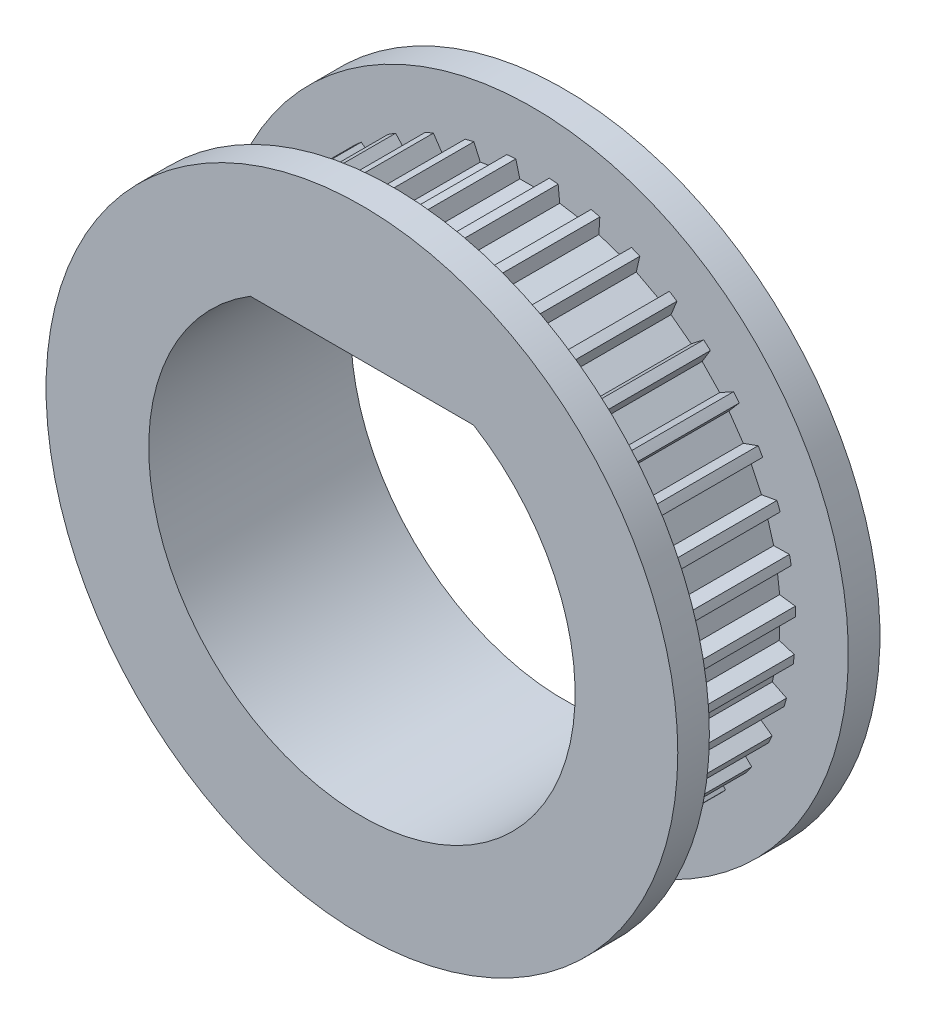
SolidWorks part; units mm, degrees
ref_plane "Front Plane" through (0, 0, 0) normal (0, 0, 1) x (1, 0, 0)
ref_plane "Top Plane" through (0, 0, 0) normal (0, 1, 0) x (1, 0, 0)
ref_plane "Right Plane" through (0, 0, 0) normal (1, 0, 0) x (0, 0, -1)
sketch "Sketch1" plane through (0, 0, 0) normal (0, 0, 1) x (1, 0, 0)
  circle A0 centre (0, 0) radius 12.5
  dimension "D1" = 25
extrude "Boss-Extrude1" add sketch "Sketch1" along normal mid plane 6.6
sketch "Sketch3" plane through (0, 0, 3.3) normal (0, 0, 1) x (1, 0, 0)
  circle A0 centre (0, 0) radius 15
  dimension "D1" = 30
sketch "Sketch2" plane through (0, 0, -3.3) normal (0, 0, -1) x (-1, 0, 0)
  circle A0 centre (0, 0) radius 15
  dimension "D1" = 30
sketch "Sketch4" plane through (0, 0, 3.3) normal (0, 0, 1) x (1, 0, 0)
  line L0 (-0.6, 11.75) -> (0.6, 11.75)
  line L1 (0.6, 11.75) -> (0.8, 12.5)
  line L2 (0.8, 12.5) -> (-0.8, 12.5)
  line L3 (-0.8, 12.5) -> (-0.6, 11.75)
  circle A0 centre (0, 0) radius 12.5 construction
  point P10 (0, 11.75)
  dimension "D1" = 1.2
  dimension "D2" = 1.6
  dimension "D3" = 0.75
extrude "Cut-Extrude1" cut sketch "Sketch4" against normal up to surface (6.6 mm away) and the other way through all up to face at (12.5, 0, -3.3)
pattern_circular "CirPattern2" count 39 over 360 about axis through (0, 0, 3.3) along (0, 0, 1) of "Cut-Extrude1"
extrude "Boss-Extrude3" add sketch "Sketch2" along normal blind 1.5
extrude "Boss-Extrude4" add sketch "Sketch3" along normal blind 1.5 contours A0
sketch "Sketch6" plane through (0, 0, 4.8) normal (0, 0, 1) x (1, 0, 0)
  line L0 (-5.3033, 8.625) -> (5.3033, 8.625)
  circle A0 centre (0, 0) radius 10.125
  point P5 (0, 10.125)
  dimension "D1" = 20.25
  dimension "D2" = 1.5
extrude "Cut-Extrude3" cut sketch "Sketch6" against normal through all both and the other way through all contours L0 A0 region at (0, -0.3194, 4.8)
